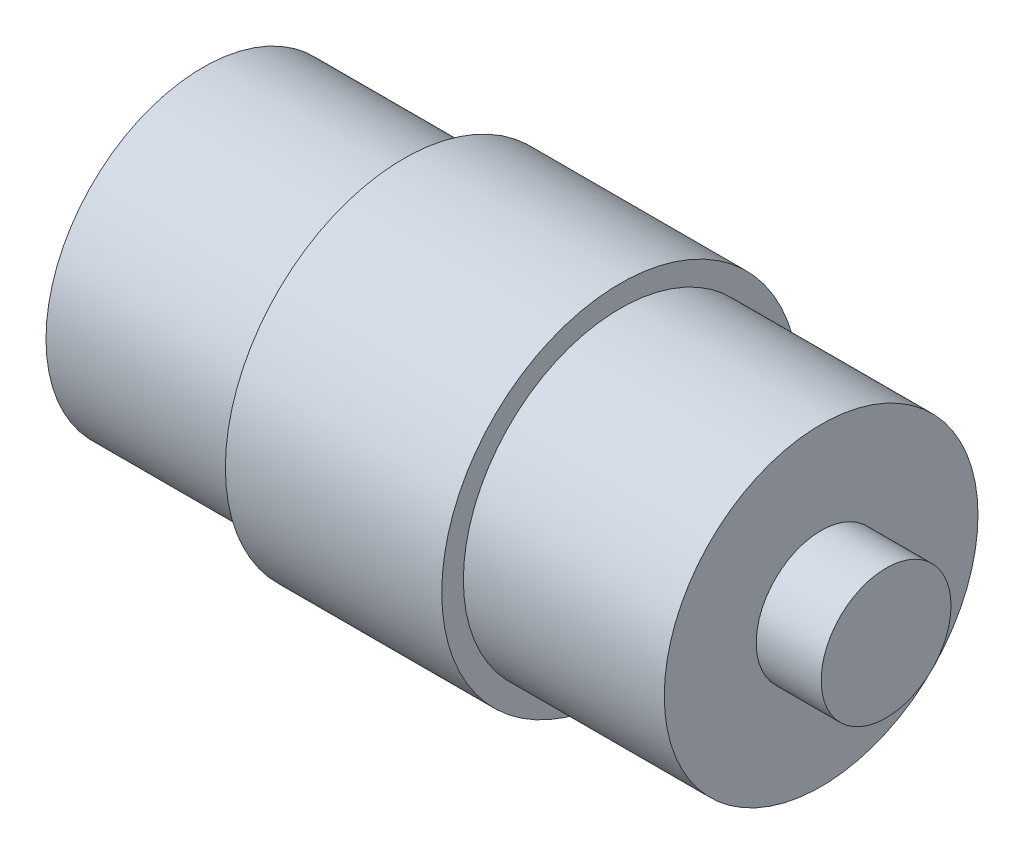
SolidWorks part; units mm, degrees
ref_plane "Front Plane" through (0, 0, 0) normal (0, 0, 1) x (1, 0, 0)
ref_plane "Top Plane" through (0, 0, 0) normal (0, 1, 0) x (1, 0, 0)
ref_plane "Right Plane" through (0, 0, 0) normal (1, 0, 0) x (0, 0, -1)
sketch "CoilBase" plane through (0, 0, 0) normal (1, 0, 0) x (0, 0, -1)
  circle A0 centre (0, 0) radius 7.25
  dimension "CoilDam" = 14.5
extrude "Boss-Extrude1" add sketch "CoilBase" along normal blind 28.575
ref_plane "Midplane" through (14.29, 0, 0) normal (1, 0, 0) x (0, 0, -1)
ref_axis "Centerline" through (-1.4288, 0, 0) along (1, 0, 0)
ref_point "COM"
sketch "WireHousing" plane through (14.29, 0, 0) normal (1, 0, 0) x (0, 0, -1)
  circle A0 centre (0, 0) radius 8.25
  dimension "MaxDiam" = 16.5
extrude "WireHousing-Extrude" add sketch "WireHousing" along normal blind 5 and the other way blind 5
sketch "ClearanceForActuator" plane through (14.29, 0, 0) normal (1, 0, 0) x (0, 0, -1)
  circle A0 centre (0, 0) radius 3
  dimension "clearD" = 6
extrude "Boss-Extrude3" add sketch "ClearanceForActuator" along normal blind 17.2875 and the other way blind 17.2875 contours A0
equation "\"L\" = 28.575mm'Length of Haptuator"
equation "\"MaxDiam\"= 16.5mm'Maximum Diameter of Haptuator"
equation "\"CoilDam\" = 14.5mm'Diam of Coils"
equation "\"Clearance\"= 3mm'Clearance for actuator"
equation "\"clearL\"= \"L\" / 2 + \"Clearance\"'required length"
equation "\"clearD\"= 6mm'Diameter of clearance space"
